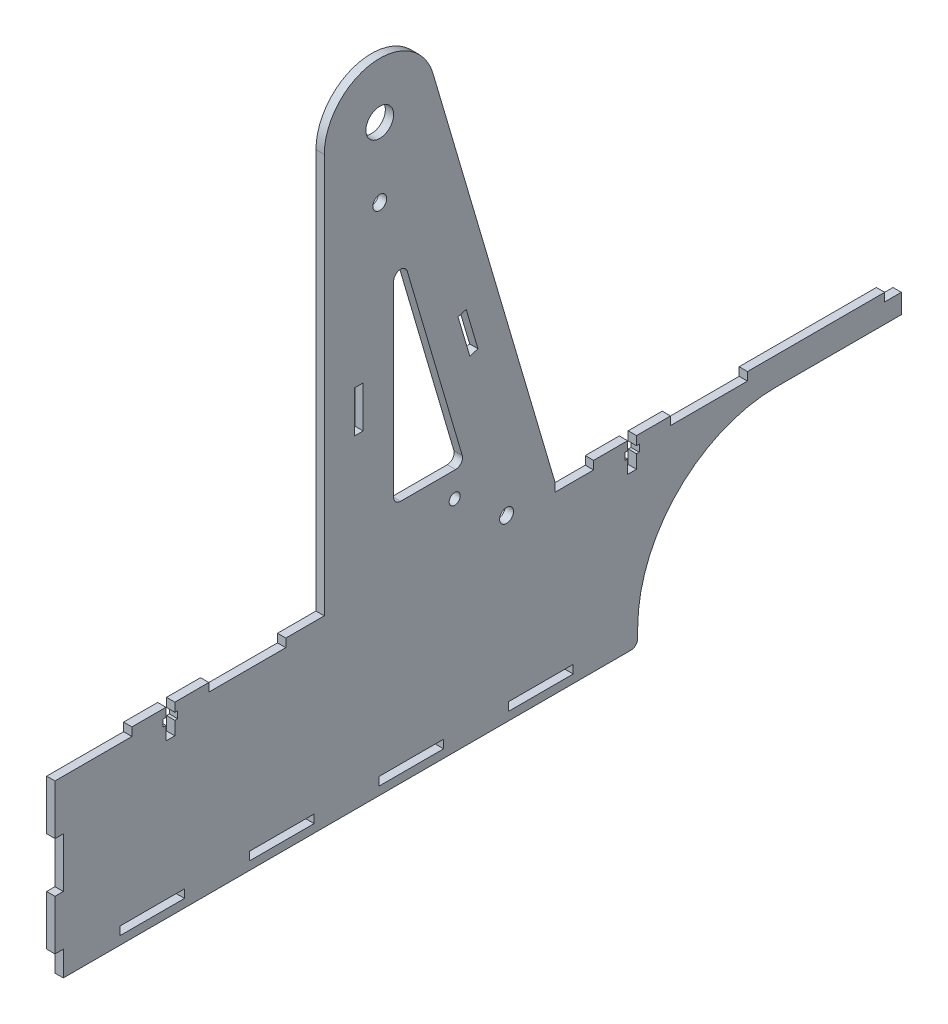
SolidWorks part; units mm, degrees
ref_plane "Front Plane" through (0, 0, 0) normal (0, 0, 1) x (1, 0, 0)
ref_plane "Top Plane" through (0, 0, 0) normal (0, 1, 0) x (1, 0, 0)
ref_plane "Right Plane" through (0, 0, 0) normal (1, 0, 0) x (0, 0, -1)
sketch "Sketch1" plane through (0, 0, 0) normal (1, 0, 0) x (0, 0, -1)
  line L0 (-152.5, 33) -> (152.5, 33)
  line L1 (152.5, 33) -> (152.5, 23)
  line L2 (-152.5, 33) -> (-152.5, -33)
  line L4 (107.5, 23) -> (152.5, 23)
  line L5 (57.5, -27) -> (57.5, -33)
  line L6 (57.5, -33) -> (-152.5, -33)
  arc A0 (57.5, -27) -> (107.5, 23) centre (107.5, -27) cw
  point P4 (-152.5, 0)
  point P7 (0, 33)
  dimension "D1" = 50
  dimension "D2" = 95
  dimension "D3" = 305
  dimension "D4" = 66
  dimension "D5" = 6
extrude "Boss-Extrude1" add sketch "Sketch1" along normal blind 3
sketch "Sketch2" plane through (3, 0, 0) normal (1, 0, 0) x (0, 0, -1)
  line L0 (-129.1567, -30) -> (-152.5, -30) construction
  line L1 (-129.1567, -30) -> (-105.8133, -30)
  line L2 (-129.1567, -30) -> (-129.1567, -27)
  line L3 (-129.1567, -27) -> (-105.8133, -27)
  line L4 (-105.8133, -30) -> (-105.8133, -27)
  line L5 (-129.1567, -30) -> (-105.8133, -27) construction
  line L6 (-129.1567, -27) -> (-105.8133, -30) construction
  line L7 (-82.47, -30) -> (-59.1266, -30)
  line L8 (-82.47, -30) -> (-82.47, -27)
  line L9 (-82.47, -27) -> (-59.1266, -27)
  line L10 (-59.1266, -30) -> (-59.1266, -27)
  line L11 (-82.47, -30) -> (-59.1266, -27) construction
  line L12 (-82.47, -27) -> (-59.1266, -30) construction
  line L13 (-35.7833, -30) -> (-12.4399, -30)
  line L14 (-35.7833, -30) -> (-35.7833, -27)
  line L15 (-35.7833, -27) -> (-12.4399, -27)
  line L16 (-12.4399, -30) -> (-12.4399, -27)
  line L17 (-35.7833, -30) -> (-12.4399, -27) construction
  line L18 (-35.7833, -27) -> (-12.4399, -30) construction
  line L19 (10.9034, -30) -> (34.2467, -30)
  line L20 (10.9034, -30) -> (10.9034, -27)
  line L21 (10.9034, -27) -> (34.2467, -27)
  line L22 (34.2467, -30) -> (34.2467, -27)
  line L23 (10.9034, -30) -> (34.2467, -27) construction
  line L24 (10.9034, -27) -> (34.2467, -30) construction
  line L25 (-152.5, 33) -> (-152.5, -33) construction
  line L26 (-105.8133, -30) -> (-82.47, -30) construction
  line L27 (-59.1266, -30) -> (-35.7833, -30) construction
  line L28 (-12.4399, -30) -> (10.9034, -30) construction
  line L29 (34.2467, -30) -> (57.5901, -30) construction
  line L30 (-152.5, -33) -> (57.5, -33) construction
  line L31 (152.5, 33) -> (-152.5, 33) construction
  line L36 (-152.5, 30) -> (-124.7727, 30)
  line L37 (-152.5, 30) -> (-152.5, 33)
  line L42 (-152.5, 33) -> (-124.7727, 33)
  line L43 (-124.7727, 30) -> (-124.7727, 33)
  line L44 (-149.5, 12) -> (-149.5, 30) construction
  line L45 (-152.5, 30) -> (-124.7727, 33) construction
  line L46 (-152.5, 33) -> (-124.7727, 30) construction
  line L47 (-149.5, -33) -> (-152.5, -33)
  line L52 (152.5, 23) -> (152.5, 33) construction
  line L53 (-97.0455, 30) -> (-69.3182, 30)
  line L54 (-97.0455, 30) -> (-97.0455, 33)
  line L55 (-97.0455, 33) -> (-69.3182, 33)
  line L56 (-69.3182, 30) -> (-69.3182, 33)
  line L57 (-97.0455, 30) -> (-69.3182, 33) construction
  line L58 (-97.0455, 33) -> (-69.3182, 30) construction
  line L59 (-41.5909, 30) -> (-13.8636, 30)
  line L60 (-41.5909, 30) -> (-41.5909, 33)
  line L61 (-41.5909, 33) -> (-13.8636, 33)
  line L62 (-13.8636, 30) -> (-13.8636, 33)
  line L63 (-41.5909, 30) -> (-13.8636, 33) construction
  line L64 (-41.5909, 33) -> (-13.8636, 30) construction
  line L65 (13.8636, 30) -> (41.5909, 30)
  line L66 (13.8636, 30) -> (13.8636, 33)
  line L67 (13.8636, 33) -> (41.5909, 33)
  line L68 (41.5909, 30) -> (41.5909, 33)
  line L69 (13.8636, 30) -> (41.5909, 33) construction
  line L70 (13.8636, 33) -> (41.5909, 30) construction
  line L71 (69.3182, 30) -> (97.0455, 30)
  line L72 (69.3182, 30) -> (69.3182, 33)
  line L73 (69.3182, 33) -> (97.0455, 33)
  line L74 (97.0455, 30) -> (97.0455, 33)
  line L75 (69.3182, 30) -> (97.0455, 33) construction
  line L76 (69.3182, 33) -> (97.0455, 30) construction
  line L77 (124.7727, 30) -> (152.5, 30)
  line L78 (124.7727, 30) -> (124.7727, 33)
  line L79 (124.7727, 33) -> (152.5, 33)
  line L80 (152.5, 30) -> (152.5, 33)
  line L81 (124.7727, 30) -> (152.5, 33) construction
  line L82 (124.7727, 33) -> (152.5, 30) construction
  line L83 (-124.7727, 30) -> (-97.0455, 30) construction
  line L84 (-69.3182, 30) -> (-41.5909, 30) construction
  line L85 (-13.8636, 30) -> (13.8636, 30) construction
  line L86 (41.5909, 30) -> (69.3182, 30) construction
  line L87 (97.0455, 30) -> (124.7727, 30) construction
  line L88 (-149.5, -33) -> (-149.5, -24)
  line L89 (-149.5, -24) -> (-152.5, -24)
  line L90 (-152.5, -33) -> (-152.5, -24)
  line L91 (-149.5, -33) -> (-152.5, -24) construction
  line L92 (-149.5, -24) -> (-152.5, -33) construction
  line L93 (-149.5, -6) -> (-152.5, -6)
  line L94 (-149.5, -6) -> (-149.5, 12)
  line L95 (-149.5, 12) -> (-152.5, 12)
  line L96 (-152.5, -6) -> (-152.5, 12)
  line L97 (-149.5, -6) -> (-152.5, 12) construction
  line L98 (-149.5, 12) -> (-152.5, -6) construction
  line L99 (-149.5, -6) -> (-149.5, -24) construction
  line L100 (146.5, 30) -> (146.5, 33)
  arc A0 (107.5, 23) -> (57.5, -27) centre (107.5, -27) ccw construction
  point P0 (-117.485, -28.5)
  point P5 (-70.7983, -28.5)
  point P10 (-24.1116, -28.5)
  point P15 (22.5751, -28.5)
  point P29 (-138.6364, 31.5)
  point P36 (-83.1818, 31.5)
  point P41 (-27.7273, 31.5)
  point P46 (27.7273, 31.5)
  point P51 (83.1818, 31.5)
  point P56 (138.6364, 31.5)
  point P61 (-151, 3)
  point P64 (-151, -28.5)
  line M15 (-152.5, 33) -> (-152.5, -33)
  line M16 (-152.5, -33) -> (57.5, -33)
  line M20 (152.5, 23) -> (152.5, 33)
  line M21 (152.5, 33) -> (-152.5, 33)
  dimension "D1" = 3
  dimension "D2" = 3
  dimension "D3" = 9
  dimension "D4" = 6
extrude "Cut-Extrude1" cut sketch "Sketch2" against normal through all both and the other way through all contours L65 L68 L66 M21 | L71 L74 L72 M21 | L36 L43 M21 M15 | L53 L56 L54 M21 | L59 L62 L60 M21 | L94 L95 L93 M15 | L88 L89 M15 M16 | L1 L4 L3 L2 | L7 L10 L9 L8 | L19 L22 L21 L20 | L100 L77 M20 M21 | L16 L15 L14 L13 region at (3, -28.5, 117.485) region at (3, -28.5, 70.7983) region at (3, -28.5, -22.5751) region at (3, 31.5, 138.6364) region at (3, 31.5, -83.1818) region at (3, 31.5, -27.7273) region at (3, 31.5, 27.7273) region at (3, 31.5, 83.1818) region at (3, -28.5, 151) region at (3, 3, 151) region at (3, 31.5, -149.5)
sketch "Sketch3" plane through (3, 0, 0) normal (1, 0, 0) x (0, 0, -1)
  line L0 (-97.0455, 33) -> (-124.7727, 33) construction
  line L1 (-112.5091, 22.5) -> (-109.3091, 22.5)
  line L2 (-112.5091, 22.5) -> (-112.5091, 33)
  line L3 (-112.5091, 33) -> (-109.3091, 33)
  line L4 (-109.3091, 22.5) -> (-109.3091, 33)
  line L5 (-112.5091, 22.5) -> (-109.3091, 33) construction
  line L6 (-112.5091, 33) -> (-109.3091, 22.5) construction
  line L7 (69.3182, 33) -> (41.5909, 33) construction
  line L8 (53.8545, 22.5) -> (57.0545, 22.5)
  line L9 (53.8545, 22.5) -> (53.8545, 33)
  line L10 (53.8545, 33) -> (57.0545, 33)
  line L11 (57.0545, 22.5) -> (57.0545, 33)
  line L12 (53.8545, 22.5) -> (57.0545, 33) construction
  line L13 (53.8545, 33) -> (57.0545, 22.5) construction
  line L14 (55.4545, 29.825) -> (55.4545, 33) construction
  line L15 (52.8545, 29.825) -> (58.0545, 29.825)
  line L16 (52.8545, 29.825) -> (52.8545, 27.325)
  line L17 (52.8545, 27.325) -> (58.0545, 27.325)
  line L18 (58.0545, 29.825) -> (58.0545, 27.325)
  line L19 (52.8545, 29.825) -> (58.0545, 27.325) construction
  line L20 (52.8545, 27.325) -> (58.0545, 29.825) construction
  line L21 (-113.5091, 29.825) -> (-108.3091, 29.825)
  line L22 (-113.5091, 29.825) -> (-113.5091, 27.325)
  line L23 (-113.5091, 27.325) -> (-108.3091, 27.325)
  line L24 (-108.3091, 29.825) -> (-108.3091, 27.325)
  line L25 (-113.5091, 29.825) -> (-108.3091, 27.325) construction
  line L26 (-113.5091, 27.325) -> (-108.3091, 29.825) construction
  line L27 (-110.9091, 29.825) -> (-110.9091, 33) construction
  point P0 (-110.9091, 27.75)
  point P7 (55.4545, 27.75)
  point P14 (55.4545, 28.575)
  point P19 (-110.9091, 28.575)
  point P24 (-110.9091, 33)
  point P25 (55.4545, 33)
  dimension "D1" = 3.2
  dimension "D2" = 10.5
  dimension "D3" = 2.5
  dimension "D4" = 5.2
  dimension "D5" = 3.175
extrude "Cut-Extrude2" cut sketch "Sketch3" against normal through all both and the other way through all contours L4 L3 L2 L1 | L23 L24 L21 L22 | L11 L10 L9 L8 | L17 L18 L15 L16
fillet "Fillet1" radius 2.5 1 edges at (1.5, -33, -57.5)
sketch "Sketch4" plane through (0, 0, 0) normal (1, 0, 0) x (0, 0, -1)
  line L0 (-55.4545, 30) -> (-55.4545, 177)
  line L2 (27.7273, 30) -> (27.7273, 33)
  line L3 (-55.4545, 30) -> (27.7273, 30)
  line L4 (-13.8636, 30) -> (-41.5909, 30) construction
  line L5 (-41.5909, 33) -> (-69.3182, 33) construction
  line L6 (27.7273, 33) -> (-16.2666, 182.6412)
  line L7 (13.8636, 33) -> (-13.8636, 33) construction
  line L8 (41.5909, 30) -> (13.8636, 30) construction
  line L9 (-149.5, -33) -> (55, -33) construction
  line L19 (-30.4545, 55) -> (-4.7987, 55)
  line L20 (-4.7987, 55) -> (-30.4545, 142.2661)
  line L21 (-30.4545, 142.2661) -> (-30.4545, 55)
  line L22 (-55.4545, 142.2661) -> (-30.4545, 142.2661) construction
  line L23 (-30.4545, 142.2661) -> (-6.4696, 149.3176) construction
  line L24 (-30.4545, 55) -> (-30.4545, 30) construction
  arc A0 (-55.4545, 177) -> (-16.2666, 182.6412) centre (-35.4545, 177) cw
  circle A1 centre (-35.4545, 177) radius 5
  point P10 (-55.4545, 33)
  point P16 (27.7273, 30)
  dimension "D2" = 10
  dimension "D3" = 15
  dimension "D1" = 210
  dimension "D4" = 25
extrude "Boss-Extrude2" add sketch "Sketch4" along normal up to surface (3 mm away) up to face at (3, -28.5, 24.1116)
fillet "Fillet2" radius 2.5 3 edges at (1.5, 55, 4.7987) (1.5, 55, 30.4545) (1.5, 142.2661, 30.4545)
ref_axis "Axis1" through (-68.2488, 177, 35.4545) along (1, 0, 0)
sketch "Sketch5" plane through (3, 0, 0) normal (1, 0, 0) x (0, 0, -1)
  line L0 (27.7273, 33) -> (27.7273, 30) construction
  line L1 (-35.4545, 152) -> (-35.4545, 177) construction
  line L2 (-3.0037, 87.8049) -> (-7.2346, 102.1958)
  line L3 (-44.4795, 83.6996) -> (-41.4295, 83.6996)
  line L4 (-44.4795, 83.6996) -> (-44.4795, 98.6996)
  line L5 (-44.4795, 98.6996) -> (-41.4295, 98.6996)
  line L6 (-41.4295, 83.6996) -> (-41.4295, 98.6996)
  line L7 (-44.4795, 83.6996) -> (-41.4295, 98.6996) construction
  line L8 (-44.4795, 98.6996) -> (-41.4295, 83.6996) construction
  line L9 (-3.0037, 87.8049) -> (-0.0775, 88.6652)
  line L10 (-7.2346, 102.1958) -> (-4.3084, 103.0561)
  line L11 (-0.0775, 88.6652) -> (-4.3084, 103.0561)
  line L12 (-3.0037, 87.8049) -> (-4.3084, 103.0561) construction
  line L13 (-7.2346, 102.1958) -> (-0.0775, 88.6652) construction
  line L14 (-55.4545, 91.1996) -> (-30.4545, 91.1996) construction
  line L15 (-55.4545, 33) -> (-55.4545, 177) construction
  line L16 (-15.6485, 91.9048) -> (8.3364, 98.9562) construction
  line L17 (-25.5561, 125.6044) -> (-5.741, 58.2051) construction
  line L18 (-16.2666, 182.6412) -> (27.7273, 33) construction
  line L19 (-30.4545, 57.5) -> (-30.4545, 124.8992) construction
  line L20 (-8.1395, 55) -> (-27.9545, 55) construction
  circle A0 centre (10.2272, 31.5) radius 2.5
  circle A1 centre (-35.4545, 152) radius 2.5
  circle A2 centre (-8.4545, 46) radius 2
  point P5 (27.7273, 31.5)
  point P7 (-42.9545, 91.1996)
  point P15 (-3.656, 95.4305)
  point P30 (-42.9545, 91.1996)
  point P31 (-3.656, 95.4305)
  point P35 (-30.4545, 91.1996)
  point P36 (-15.6485, 91.9048)
  dimension "D2" = 5
  dimension "D6" = 4
  dimension "D1" = 17.5001
  dimension "D3" = 25
  dimension "D4" = 3.05
  dimension "D5" = 15
  dimension "D7" = 9
  dimension "D8" = 22
extrude "Cut-Extrude3" cut sketch "Sketch5" against normal through all both and the other way through all
